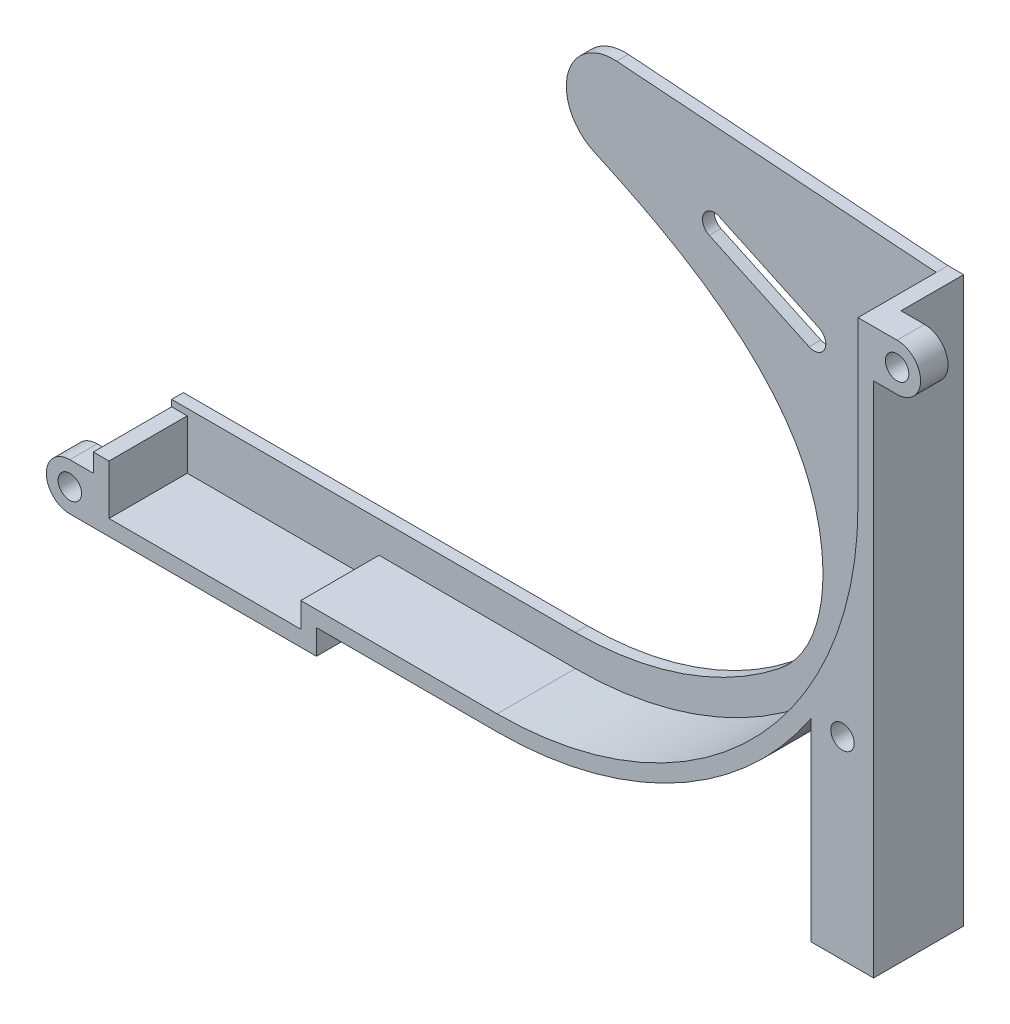
SolidWorks part; units mm, degrees
ref_plane "Front Plane" through (0, 0, 0) normal (0, 0, 1) x (1, 0, 0)
ref_plane "Top Plane" through (0, 0, 0) normal (0, 1, 0) x (1, 0, 0)
ref_plane "Right Plane" through (0, 0, 0) normal (1, 0, 0) x (0, 0, -1)
sketch "Sketch1" plane through (0, 0, 0) normal (0, 0, 1) x (1, 0, 0)
  line L0 (-18.1262, 8.4524) -> (18.1262, -8.4524) construction
  line L1 (0, 0) -> (25.201, 0) construction
  line L2 (23.1262, 11.4863) -> (23.1262, -9.2963)
  line L3 (-22.9677, -55.3901) -> (-48.0407, -55.3901)
  line L4 (-48.0407, -55.3901) -> (-48.0407, -58.5651)
  line L5 (-48.0407, -58.5651) -> (-72.5407, -58.5651)
  line L6 (-72.5407, -58.5651) -> (-72.5407, -52.2151)
  line L7 (25.1262, 11.4863) -> (25.1262, -9.2963)
  line L8 (-22.9677, -57.3901) -> (-46.0407, -57.3901)
  line L9 (-46.0407, -57.3901) -> (-46.0407, -60.5651)
  line L10 (-46.0407, -60.5651) -> (-74.5407, -60.5651)
  line L11 (-74.5407, -60.5651) -> (-74.5407, -52.2151)
  line L12 (-72.5407, -52.2151) -> (-74.5407, -52.2151)
  line L13 (23.1262, 11.4863) -> (25.1262, 11.4863)
  arc A0 (23.1262, -9.2963) -> (-22.9677, -55.3901) centre (-22.9677, -9.2963) cw
  arc A1 (25.1262, -9.2963) -> (-22.9677, -57.3901) centre (-22.9677, -9.2963) cw
  point P3 (0, 0)
  dimension "D1" = 40
  dimension "D2" = 25
  dimension "D3" = 5
  dimension "D4" = 24.5
  dimension "D5" = 3.175
  dimension "D6" = 6.35
  dimension "D7" = 2
extrude "Boss-Extrude1" add sketch "Sketch1" along normal blind 10
sketch "Sketch2" plane through (0, 0, 0) normal (0, 0, -1) x (-1, 0, 0)
  line L1 (-23.1262, 11.4863) -> (17.6936, 14.4368)
  line L4 (18.1262, 8.4524) -> (-18.1262, -8.4524) construction
  line L5 (-7.5168, -3.5051) -> (5.2321, 2.4397) construction
  line L6 (-8.1507, -2.1457) -> (4.5981, 3.7992)
  line L7 (-6.8829, -4.8646) -> (5.866, 1.0803)
  line L11 (52.0407, -51.3901) -> (74.5407, -51.3901)
  line L38 (74.5407, -51.3901) -> (74.5407, -52.2151)
  line L39 (-25.1262, 11.4863) -> (-23.1262, 11.4863)
  line L48 (-19.1262, -9.2963) -> (-19.1262, 15.4863)
  line L49 (-19.1262, 15.4863) -> (-29.1262, 15.4863)
  line L50 (-29.1262, 15.4863) -> (-29.1262, -9.2963)
  line L51 (22.9677, -61.3901) -> (42.0407, -61.3901)
  line L52 (42.0407, -61.3901) -> (42.0407, -64.5651)
  line L53 (42.0407, -64.5651) -> (78.5407, -64.5651)
  line L54 (78.5407, -64.5651) -> (78.5407, -48.2151)
  line L55 (78.5407, -48.2151) -> (68.5407, -48.2151)
  line L56 (68.5407, -48.2151) -> (68.5407, -54.5651)
  line L57 (68.5407, -54.5651) -> (52.0407, -54.5651)
  line L58 (52.0407, -54.5651) -> (52.0407, -51.3901)
  line L59 (52.0407, -51.3901) -> (22.9677, -51.3901)
  line L71 (52.0407, -51.3901) -> (22.9677, -51.3901)
  line L74 (-23.1262, 11.4863) -> (-25.1262, 11.4863)
  line L75 (-25.1262, 11.4863) -> (-25.1262, -9.2963)
  line L76 (22.9677, -57.3901) -> (46.0407, -57.3901)
  line L77 (46.0407, -57.3901) -> (46.0407, -60.5651)
  line L78 (46.0407, -60.5651) -> (74.5407, -60.5651)
  line L79 (74.5407, -60.5651) -> (74.5407, -52.2151)
  line L80 (74.5407, -52.2151) -> (72.5407, -52.2151)
  line L81 (72.5407, -52.2151) -> (72.5407, -58.5651)
  line L82 (72.5407, -58.5651) -> (48.0407, -58.5651)
  line L83 (48.0407, -58.5651) -> (48.0407, -55.3901)
  line L84 (48.0407, -55.3901) -> (22.9677, -55.3901)
  line L85 (-23.1262, -9.2963) -> (-23.1262, 11.4863)
  line L87 (-25.1262, 11.4863) -> (-25.1262, -9.2963)
  line L88 (22.9677, -57.3901) -> (46.0407, -57.3901)
  line L89 (46.0407, -57.3901) -> (46.0407, -60.5651)
  line L90 (46.0407, -60.5651) -> (74.5407, -60.5651)
  line L91 (74.5407, -60.5651) -> (74.5407, -52.2151)
  arc A1 (20.6619, 3.0145) -> (17.6936, 14.4368) centre (18.1262, 8.4524) ccw
  arc A6 (-8.1507, -2.1457) -> (-6.8829, -4.8646) centre (-7.5168, -3.5051) ccw
  arc A7 (5.866, 1.0803) -> (4.5981, 3.7992) centre (5.2321, 2.4397) ccw
  arc A8 (-29.1262, -9.2963) -> (22.9677, -61.3901) centre (22.9677, -9.2963) ccw
  arc A9 (-19.1262, -9.2963) -> (22.9677, -51.3901) centre (22.9677, -9.2963) ccw
  arc A11 (-3.1097, -42.3396) -> (22.9677, -51.3901) centre (22.9677, -9.2963) ccw
  arc A12 (-25.1262, -9.2963) -> (22.9677, -57.3901) centre (22.9677, -9.2963) ccw
  arc A13 (-23.1262, -9.2963) -> (22.9677, -55.3901) centre (22.9677, -9.2963) ccw
  arc A14 (-25.1262, -9.2963) -> (22.9677, -57.3901) centre (22.9677, -9.2963) ccw
  spline S0 degree 3 poles (20.6619, 3.0145) (14.467, 0.1258) (-11.1415, -11.2332) (-9.493, -37.302) (-3.1097, -42.3396) knots 0 0 0 0 0.582936 1 1 1 1
  point P20 (-1.1424, -0.5327)
  dimension "D3" = 1.5
  dimension "D4" = 6
  dimension "D1" = 4
  dimension "D2" = 0
extrude "Boss-Extrude2" add sketch "Sketch2" along normal blind 1.5
sketch "Sketch4" plane through (0, 0, -1.5) normal (0, 0, -1) x (-1, 0, 0)
  line L0 (-25.1262, -9.2963) -> (-25.1262, -60.5651)
  line L1 (-25.1262, -60.5651) -> (-17.1262, -60.5651)
  line L2 (-17.1262, -60.5651) -> (-17.1262, -35.8576)
  line L3 (46.0407, -60.5651) -> (74.5407, -60.5651) construction
  line L4 (-28.1262, 11.4863) -> (-25.1262, 11.4863)
  line L5 (-28.1262, 5.4863) -> (-25.1262, 5.4863)
  line L6 (-25.1262, 11.4863) -> (-25.1262, -9.2963) construction
  line L7 (-25.1262, 11.4863) -> (-25.1262, 5.4863)
  line L8 (74.5407, -60.5651) -> (74.5407, -51.3901) construction
  line L9 (74.5407, -60.5651) -> (74.5407, -54.5651)
  line L10 (74.5407, -60.5651) -> (77.5407, -60.5651)
  line L11 (77.5407, -54.5651) -> (74.5407, -54.5651)
  arc A0 (-25.1262, -9.2963) -> (22.9677, -57.3901) centre (22.9677, -9.2963) ccw construction
  arc A3 (-28.1262, 11.4863) -> (-28.1262, 5.4863) centre (-28.1262, 8.4863) ccw
  arc A4 (77.5407, -60.5651) -> (77.5407, -54.5651) centre (77.5407, -57.5651) ccw
  arc A5 (-25.1262, -9.2963) -> (22.9677, -57.3901) centre (22.9677, -9.2963) ccw construction
  arc A6 (-25.1262, -9.2963) -> (-17.1262, -35.8576) centre (22.9677, -9.2963) ccw
  circle A7 centre (-28.1262, 8.4863) radius 1.5
  circle A8 centre (77.5407, -57.5651) radius 1.5
  circle A9 centre (-21.1479, -35.8576) radius 1.5
  dimension "D2" = 3
  dimension "D3" = 6
  dimension "D4" = 3
  dimension "D5" = 3
  dimension "D1" = 8
extrude "Boss-Extrude3" add sketch "Sketch4" against normal up to surface (11.5 mm away) up to face at (-29.4464, -41.6699, 10)
sketch "Sketch5" plane through (0, 0, -1.5) normal (0, 0, -1) x (-1, 0, 0)
  line L0 (-25.1262, 5.4863) -> (-25.1262, 11.4863)
  line L1 (74.5407, -54.5651) -> (74.5407, -60.5651)
  line L12 (-23.1262, 11.4863) -> (-28.1262, 11.4863)
  line L13 (-28.1262, 5.4863) -> (-25.1262, 5.4863)
  line L14 (-25.1262, 5.4863) -> (-25.1262, -60.5651)
  line L15 (-25.1262, -60.5651) -> (-17.1262, -60.5651)
  line L16 (-17.1262, -60.5651) -> (-17.1262, -35.8576)
  line L17 (22.9677, -57.3901) -> (46.0407, -57.3901)
  line L18 (46.0407, -57.3901) -> (46.0407, -60.5651)
  line L19 (46.0407, -60.5651) -> (77.5407, -60.5651)
  line L20 (77.5407, -54.5651) -> (74.5407, -54.5651)
  line L21 (74.5407, -54.5651) -> (74.5407, -51.3901)
  line L22 (74.5407, -51.3901) -> (22.9677, -51.3901)
  line L23 (17.6936, 14.4368) -> (-23.1262, 11.4863)
  line L24 (-25.1262, 11.4863) -> (-28.1262, 11.4863)
  line L25 (-28.1262, 5.4863) -> (-25.1262, 5.4863)
  line L31 (74.5407, -60.5651) -> (77.5407, -60.5651)
  line L32 (77.5407, -54.5651) -> (74.5407, -54.5651)
  arc A1 (77.5407, -60.5651) -> (77.5407, -54.5651) centre (77.5407, -57.5651) ccw
  arc A2 (77.5407, -60.5651) -> (77.5407, -54.5651) centre (77.5407, -57.5651) ccw construction
  circle A3 centre (-21.1479, -35.8576) radius 3
  arc A9 (-28.1262, 11.4863) -> (-28.1262, 5.4863) centre (-28.1262, 8.4863) ccw
  arc A10 (-17.1262, -35.8576) -> (22.9677, -57.3901) centre (22.9677, -9.2963) ccw
  arc A11 (77.5407, -60.5651) -> (77.5407, -54.5651) centre (77.5407, -57.5651) ccw
  arc A12 (-3.1097, -42.3396) -> (22.9677, -51.3901) centre (22.9677, -9.2963) ccw
  arc A13 (20.6619, 3.0145) -> (17.6936, 14.4368) centre (18.1262, 8.4524) ccw
  arc A14 (-28.1262, 11.4863) -> (-28.1262, 5.4863) centre (-28.1262, 8.4863) ccw
  arc A16 (77.5407, -60.5651) -> (77.5407, -54.5651) centre (77.5407, -57.5651) ccw
  spline S1 degree 3 poles (457.0873, 845.4694) (81.3885, -175.3064) (-156.9601, 73.8373) (229.1068, -13.9969) (-977.9948, -48.7502) knots -1.766509 -1.766509 -1.766509 -1.766509 0.417064 3.019761 3.019761 3.019761 3.019761 only from (-3.1097, -42.3396) to (20.6619, 3.0145)
  line M3 (-23.1262, 11.4863) -> (-28.1262, 11.4863)
  arc M4 (-28.1262, 11.4863) -> (-28.1262, 5.4863) centre (-28.1262, 8.4863) ccw
  line M5 (-28.1262, 5.4863) -> (-25.1262, 5.4863)
  line M12 (46.0407, -60.5651) -> (77.5407, -60.5651)
  arc M13 (77.5407, -60.5651) -> (77.5407, -54.5651) centre (77.5407, -57.5651) ccw
  line M14 (77.5407, -54.5651) -> (74.5407, -54.5651)
  circle M25 centre (-21.1479, -35.8576) radius 1.5
  circle M26 centre (-28.1262, 8.4863) radius 1.5
  circle M27 centre (77.5407, -57.5651) radius 1.5
  dimension "D1" = 6
  dimension "D2" = 0
extrude "Cut-Extrude1" cut sketch "Sketch5" against normal blind 8 contours L1 M14 M12 M13 M27 | A3 M25 | L0 M5 M3 M4 M26 region at (26.6262, 5.5712, -1.5) region at (-74.6255, -57.5651, -1.5) region at (24.0631, -35.8576, -1.5)
